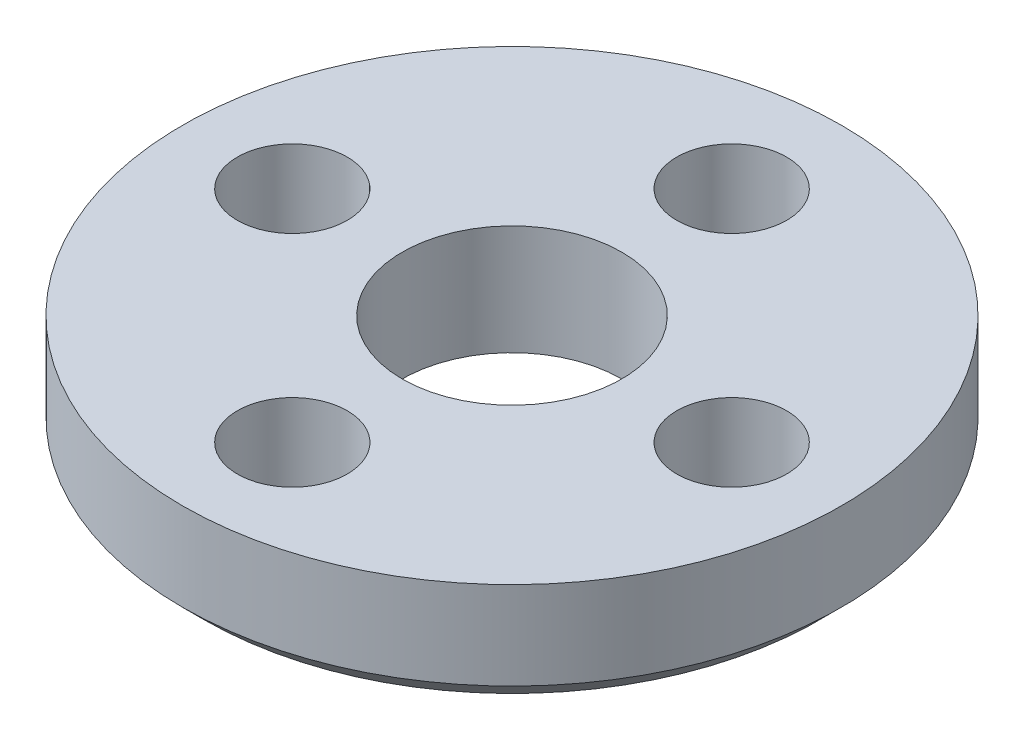
SolidWorks part; units mm, degrees
ref_plane "Front Plane" through (0, 0, 0) normal (0, 0, 1) x (1, 0, 0)
ref_plane "Top Plane" through (0, 0, 0) normal (0, 1, 0) x (1, 0, 0)
ref_plane "Right Plane" through (0, 0, 0) normal (1, 0, 0) x (0, 0, -1)
sketch "Sketch1" plane through (0, 0, 0) normal (0, 1, 0) x (1, 0, 0)
  line L0 (5, 0) -> (-5, 0) construction
  line L1 (0, 15) -> (0, 5) construction
  circle A0 centre (0, 0) radius 5
  circle A1 centre (0, 0) radius 15
  circle A2 centre (0, 10) radius 2.5
  point P10 (0, 10)
  point P20 (0, 0)
  dimension "D1" = 5
  dimension "D2" = 30
  dimension "D3" = 10
extrude "Boss-Extrude1" add sketch "Sketch1" against normal blind 5 contours A1 A2 A0 | A2 region at (-14.5757, 0, 0)
extrude "Cut-Extrude1" cut sketch "Sketch1<3>" against normal blind 5 contours A2 region at (0, 0, -10)
sketch "Sketch1<3>" plane through (0, 0, 0) normal (0, 1, 0) x (1, 0, 0) same geometry as "Sketch1"
pattern_circular "CirPattern1" count 4 over 360 about axis through (0, -5, 0) along (0, 1, 0) of "Cut-Extrude1"
chamfer "Chamfer1" distance 1 angle 45 1 edges at (0, -5, 15)
